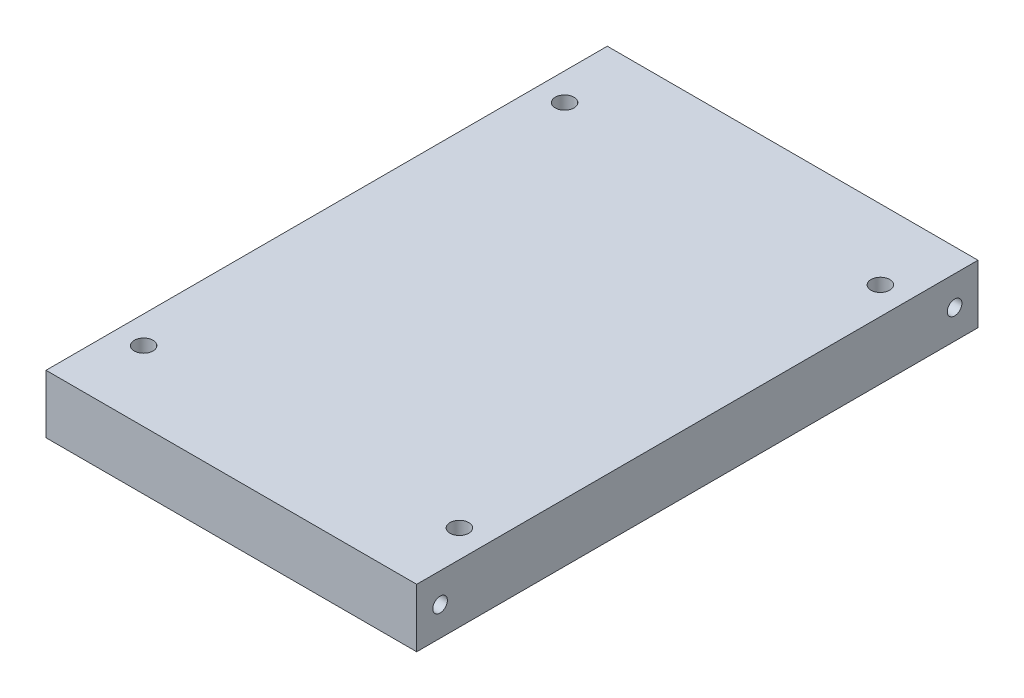
SolidWorks part; units mm, degrees
ref_plane "Front Plane" through (0, 0, 0) normal (0, 0, 1) x (1, 0, 0)
ref_plane "Top Plane" through (0, 0, 0) normal (0, 1, 0) x (1, 0, 0)
ref_plane "Right Plane" through (0, 0, 0) normal (1, 0, 0) x (0, 0, -1)
sketch "Sketch1" plane through (0, 316.5667, 0) normal (0, -1, 0) x (1, 0, 0)
  line L0 (-27, 59.5843) -> (27, -12.4157) construction
  line L1 (31.7, 100) -> (31.7, -20) construction
  line L2 (27, 59.5843) -> (-27, -12.4157) construction
  line L3 (-31.7, -24.4157) -> (31.7, -24.4157)
  line L4 (-31.7, -24.4157) -> (-31.7, 71.5843)
  line L5 (-31.7, 71.5843) -> (31.7, 71.5843)
  line L6 (31.7, -24.4157) -> (31.7, 71.5843)
  line L7 (-31.7, -24.4157) -> (31.7, 71.5843) construction
  line L8 (-31.7, 71.5843) -> (31.7, -24.4157) construction
  line L10 (-20.8, 71.5843) -> (20.8, 71.5843) construction
  circle A0 centre (-27, 59.5843) radius 1.6
  circle A1 centre (27, 59.5843) radius 1.6
  circle A2 centre (-27, -12.4157) radius 1.6
  circle A3 centre (27, -12.4157) radius 1.6
  point P8 (0, 23.5843)
  dimension "D1" = 3.2
extrude "Boss-Extrude1" add sketch "Sketch1" along normal blind 10
sketch "Sketch2" plane through (-31.7, 0, 0) normal (-1, 0, 0) x (0, 0, 1)
  line L0 (-24.4157, 311.5667) -> (71.5843, 311.5667) construction
  line L1 (-24.4157, 306.5667) -> (-24.4157, 316.5667) construction
  line L2 (71.5843, 306.5667) -> (71.5843, 316.5667) construction
  circle A0 centre (-20.4157, 311.5667) radius 1.25
  circle A1 centre (67.5843, 311.5667) radius 1.25
  dimension "D1" = 2.5
  dimension "D2" = 4
  dimension "D3" = 4
extrude "Cut-Extrude1" cut sketch "Sketch2" against normal blind 10
mirror "Mirror1" about plane through (0, 0, 0) normal (1, 0, 0) of "Cut-Extrude1"
